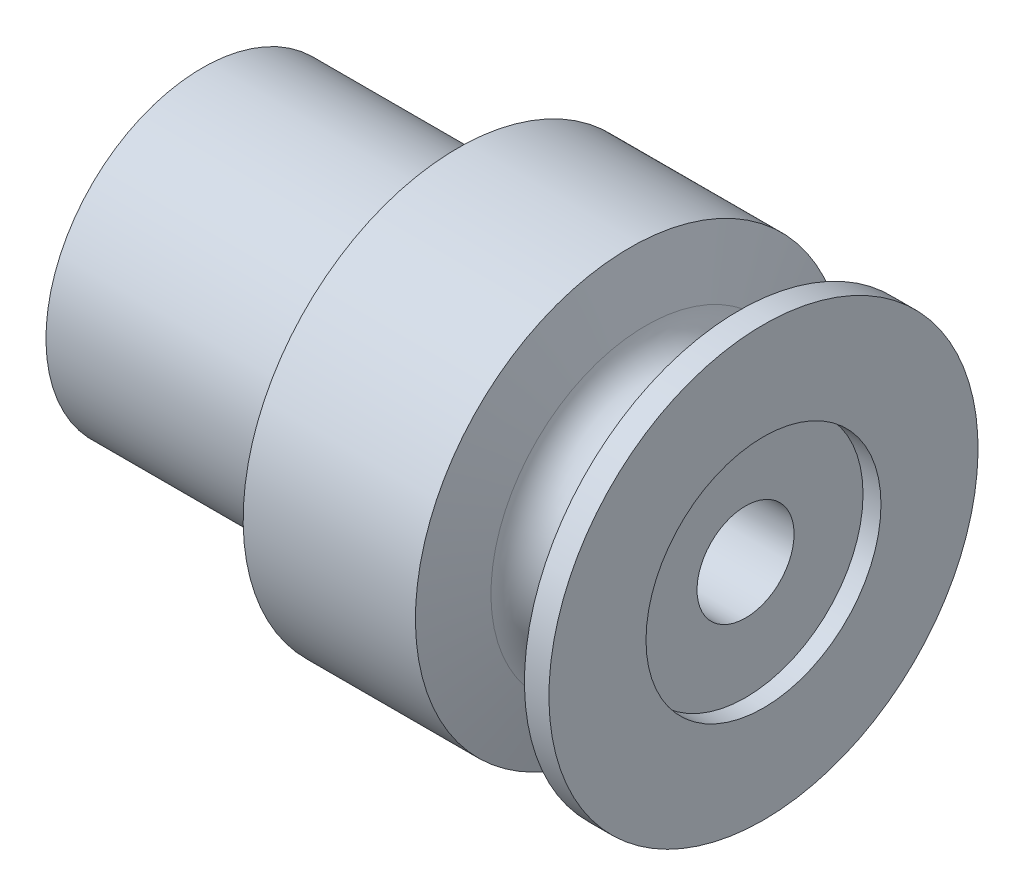
SolidWorks part; units mm, degrees
material "ABS"
ref_plane "Front" through (0, 0, 0) normal (0, 0, 1) x (1, 0, 0)
ref_plane "Top" through (0, 0, 0) normal (0, 1, 0) x (1, 0, 0)
ref_plane "Right" through (0, 0, 0) normal (1, 0, 0) x (0, 0, -1)
ref_axis "side-side" through (80.9, 0, 0) along (-1, 0, 0)
ref_axis "up-down" through (0, 50, 0) along (0, -1, 0)
ref_axis "front-back" through (0, 0, -80.9) along (0, 0, 1)
sketch "Sketch1" plane through (0, 0, 0) normal (0, 0, 1) x (1, 0, 0)
  line L3 (0, -50) -> (0, 50) construction
  line L10 (-2.5193, 7.7065) -> (-1.7257, 10.668)
  line L11 (-6.3528, 7.7065) -> (-7.1463, 10.668)
  line L12 (-15.7121, 7.7724) -> (-15.7121, 10.668)
  line L13 (-28.4121, 7.7724) -> (-15.7121, 7.7724)
  line L14 (-28.4121, 7.7724) -> (-28.4121, 6.7564)
  line L15 (-24.0687, 2.413) -> (-1.4, 2.413)
  line L16 (-1.4, 2.413) -> (-1.4, 5.842)
  line L17 (-0.508, 5.842) -> (-1.4, 5.842)
  line L18 (-0.508, 10.668) -> (-0.508, 5.842)
  line L19 (-15.7121, 10.668) -> (-7.1463, 10.668)
  line L20 (-22.5988, 0) -> (8.0828, 0) construction
  line L21 (80.9, 0) -> (-80.9, 0) construction
  line L23 (-1.7257, 10.668) -> (-0.508, 10.668)
  line L24 (-28.4121, 6.7564) -> (-24.0687, 2.413)
  arc A1 (-6.3528, 7.7065) -> (-2.5193, 7.7065) centre (-4.436, 8.2201) ccw
  dimension "D12" = 1.9844
  dimension "D1" = 30
  dimension "D2" = 15.5448
  dimension "D3" = 4.826
  dimension "D4" = 11.684
  dimension "D5" = 21.336
  dimension "D6" = 0.892
  dimension "D7" = 27.0121
  dimension "D8" = 8.5658
  dimension "D9" = 45
  dimension "D10" = 1.016
  dimension "D11" = 16.4401
  dimension "D13" = 0.508
  dimension "D14" = 12.7
  dimension "D15" = 4.436
  dimension "D16" = 1.4
revolve "Revolve1" add sketch "Sketch1" angle 360 about L20
